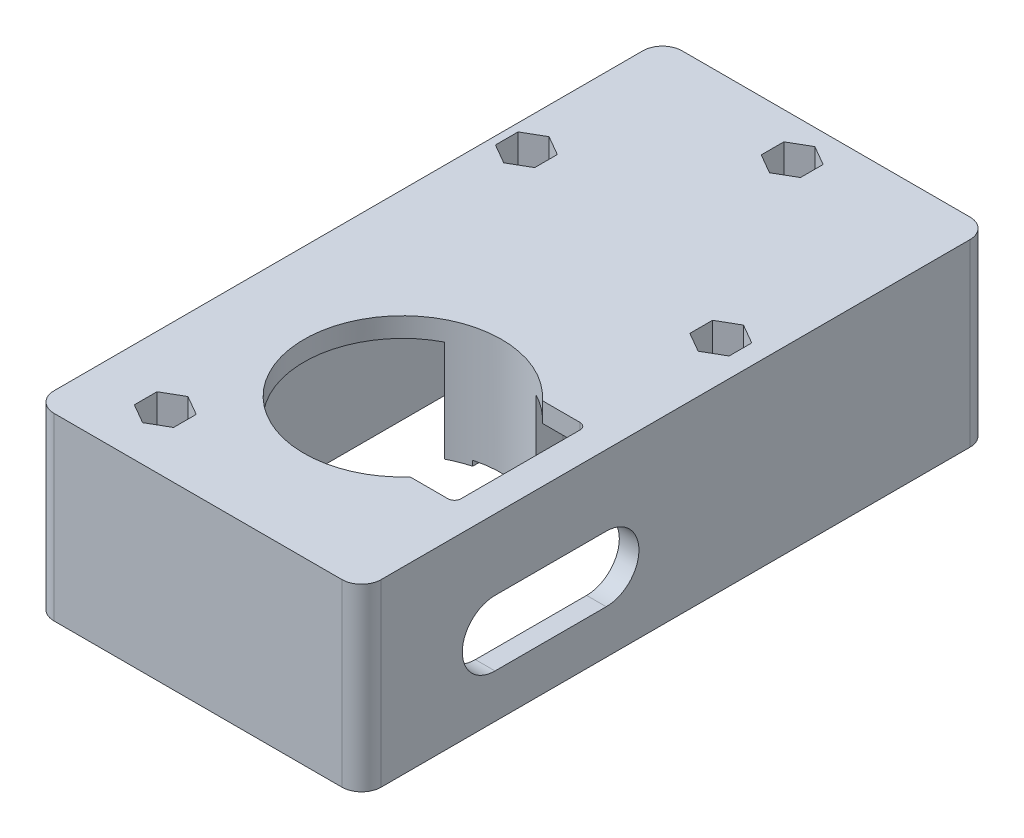
SolidWorks part; units mm, degrees
ref_plane "前视基准面" through (0, 0, 0) normal (0, 0, 1) x (1, 0, 0)
ref_plane "上视基准面" through (0, 0, 0) normal (0, 1, 0) x (1, 0, 0)
ref_plane "右视基准面" through (0, 0, 0) normal (1, 0, 0) x (0, 0, -1)
sketch "草图1" plane through (0, 0, 0) normal (0, 0, 1) x (1, 0, 0)
  line L1 (50, 38) -> (0, 38)
  line L2 (50, 38) -> (50, 0)
  line L3 (50, 0) -> (0, 0)
  line L4 (0, 38) -> (0, 0)
  dimension "D1" = 50
  dimension "D2" = 38
extrude "凸台-拉伸1" add sketch "草图1" against normal blind 3
sketch "草图2" plane through (0, 0, 0) normal (0, 0, 1) x (1, 0, 0)
  line L8 (50, 0) -> (50, 38)
  line L9 (50, 38) -> (0, 38)
  line L10 (0, 38) -> (0, 0)
  line L11 (0, 0) -> (50, 0)
  line L12 (50, 0) -> (50, 38)
  line L13 (50, 38) -> (0, 38)
  line L14 (0, 38) -> (0, 0)
  line L15 (0, 0) -> (50, 0)
  line L20 (47, 3) -> (47, 35)
  line L21 (47, 35) -> (3, 35)
  line L22 (3, 35) -> (3, 3)
  line L23 (3, 3) -> (47, 3)
  line L24 (47, 3) -> (47, 35)
  line L25 (47, 35) -> (3, 35)
  line L26 (3, 35) -> (3, 3)
  line L27 (3, 3) -> (47, 3)
  dimension "D1" = 0
  dimension "D2" = 3
extrude "凸台-拉伸2" add sketch "草图2" along normal blind 90
sketch "草图4" plane through (0, 0, -3) normal (0, 0, -1) x (-1, 0, 0)
  line L0 (-50, 38) -> (0, 38) construction
  line L1 (0, 38) -> (0, 0) construction
  circle A0 centre (-12.5, 10.5) radius 7.3
  dimension "D1" = 14.6
  dimension "D3" = 12.5
  dimension "D2" = 27.5
extrude "切除-拉伸1" cut sketch "草图4" against normal blind 45.2
sketch "草图5" plane through (0, 0, 0) normal (0, 0, 1) x (1, 0, 0)
  circle A0 centre (12.5, 10.5) radius 7.3
  circle A1 centre (12.5, 10.5) radius 7.3 construction
  circle A2 centre (12.5, 10.5) radius 10.3
  dimension "D1" = 3
extrude "凸台-拉伸3" add sketch "草图5" along normal blind 16
sketch "草图6" plane through (0, 0, -3) normal (0, 0, -1) x (-1, 0, 0)
  circle A0 centre (-12.5, 10.5) radius 5.8
  circle A3 centre (-12.5, 10.5) radius 7.3 construction
  circle A4 centre (-12.5, 10.5) radius 8.3
  circle A5 centre (-12.5, 10.5) radius 8.3
  dimension "D1" = 1
  dimension "D2" = 1.5
extrude "凸台-拉伸5" add sketch "草图6" against normal blind 1
sketch "草图7" plane through (0, 0, 16) normal (0, 0, 1) x (1, 0, 0)
  line L2 (5.4403, 3) -> (19.5597, 3)
  line L4 (5.4403, 3) -> (19.5597, 3)
  line L5 (3, 14.4799) -> (3, 6.5201)
  line L8 (3, 14.4799) -> (3, 6.5201)
  arc A1 (3, 6.5201) -> (5.4403, 3) centre (12.5, 10.5) ccw
  arc A2 (3, 6.5201) -> (5.4403, 3) centre (12.5, 10.5) ccw
  circle A3 centre (12.5, 10.5) radius 4.3
  arc A10 (19.5597, 3) -> (3, 14.4799) centre (12.5, 10.5) ccw
  arc A11 (19.5597, 3) -> (3, 14.4799) centre (12.5, 10.5) ccw
  dimension "D2" = 8.6
  dimension "D1" = 0
extrude "凸台-拉伸6" add sketch "草图7" along normal blind 2
sketch "草图8" plane through (0, 0, 18) normal (0, 0, 1) x (1, 0, 0)
  circle A1 centre (12.5, 10.5) radius 6.3
  circle A2 centre (12.5, 10.5) radius 4.3
  circle A3 centre (12.5, 10.5) radius 4.3
  dimension "D1" = 0
  dimension "D2" = 2
extrude "凸台-拉伸7" add sketch "草图8" along normal blind 10
sketch "草图9" plane through (0, 0, 28) normal (0, 0, 1) x (1, 0, 0)
  line L0 (8.2, 10.5) -> (16.8, 10.5) construction
  line L2 (16.1644, 8.25) -> (18.8, 8.25)
  line L3 (16.1644, 8.25) -> (16.1644, 12.75)
  line L4 (16.1644, 12.75) -> (18.8, 12.75)
  line L5 (18.8, 8.25) -> (18.8, 12.75)
  circle A0 centre (12.5, 10.5) radius 4.3 construction
  circle A1 centre (12.5, 10.5) radius 6.3 construction
  dimension "D1" = 4.5
extrude "切除-拉伸2" cut sketch "草图9" against normal blind 4
sketch "草图10" plane through (0, 3, 0) normal (0, 1, 0) x (1, 0, 0)
  line L0 (19.33, -36.76) -> (19.33, -34.76)
  line L1 (19.33, -34.76) -> (22.03, -34.76)
  line L2 (22.03, -34.76) -> (22.03, -36.76)
  line L3 (22.03, -36.76) -> (19.33, -36.76)
  line L8 (23.23, -37.46) -> (23.23, -28) construction
  line L9 (23.43, -37.46) -> (23.03, -37.46) construction
  line L10 (16.8, -28) -> (29.66, -28) construction
  line L11 (27.13, -34.76) -> (24.43, -34.76)
  line L12 (24.43, -34.76) -> (24.43, -36.76)
  line L13 (24.43, -36.76) -> (27.13, -36.76)
  line L14 (27.13, -36.76) -> (27.13, -34.76)
  line L15 (18.53, -37.26) -> (18.53, -34.14) construction
  line L16 (22.83, -37.26) -> (22.83, -34.14) construction
  line L17 (20.92, -34.36) -> (18.92, -34.36) construction
  circle A0 centre (19.92, -32.88) radius 0.7
  circle A1 centre (26.54, -32.88) radius 0.7
  circle A2 centre (19.92, -32.88) radius 0.98 construction
  point P14 (18.53, -35.7)
  dimension "D1" = 1.4
  dimension "D2" = 0.28
  dimension "D3" = 0.8
  dimension "D4" = 0.8
  dimension "D5" = 0.4
  dimension "D6" = 2
extrude "凸台-拉伸8" add sketch "草图10" along normal blind 32
sketch "草图11" plane through (0, 3, 0) normal (0, 1, 0) x (1, 0, 0)
  line L0 (16.8, -34.14) -> (16.8, -28) construction
  line L1 (16.2, -36.76) -> (30.26, -36.76)
  line L2 (16.2, -36.76) -> (16.2, -27.4)
  line L3 (16.2, -27.4) -> (30.26, -27.4)
  line L4 (30.26, -36.76) -> (30.26, -27.4)
  line L5 (29.66, -28) -> (29.66, -34.14) construction
  line L6 (19.33, -36.76) -> (22.03, -36.76) construction
  line L7 (16.8, -28) -> (29.66, -28) construction
  dimension "D1" = 0.6
  dimension "D2" = 0.6
  dimension "D3" = 0.6
extrude "凸台-拉伸9" add sketch "草图11" along normal blind 4.4
sketch "草图12" plane through (0, 35, 0) normal (0, -1, 0) x (1, 0, 0)
  line L1 (16.2, 27.4) -> (30.26, 27.4)
  line L2 (16.2, 27.4) -> (16.2, 36.76)
  line L3 (16.2, 36.76) -> (30.26, 36.76)
  line L4 (30.26, 27.4) -> (30.26, 36.76)
extrude "凸台-拉伸10" add sketch "草图12" along normal blind 21.2
sketch "草图13" plane through (0, 38, 0) normal (0, 1, 0) x (1, 0, 0)
  line L0 (12.3, -64.096) -> (42.5, -64.096) construction
  line L1 (40.04, -72.896) -> (39.0237, -72.896) construction
  line L2 (38.625, -74.196) -> (44.4, -74.196)
  line L3 (45.4, -73.196) -> (45.4, -54.996)
  line L4 (44.4, -57.796) -> (44.4, -70.396) construction
  line L5 (38.625, -53.996) -> (44.4, -53.996)
  circle A0 centre (27.4, -64.096) radius 15.1 construction
  circle A1 centre (27.4, -64.096) radius 14.1 construction
  arc A2 (38.625, -74.196) -> (38.625, -53.996) centre (27.4, -64.096) cw
  arc A3 (44.4, -53.996) -> (45.4, -54.996) centre (44.4, -54.996) cw
  arc A4 (44.4, -74.196) -> (45.4, -73.196) centre (44.4, -73.196) ccw
  point P16 (45.4, -64.096)
  point P18 (45.4, -53.996)
  point P21 (45.4, -74.196)
  dimension "D1" = 1
  dimension "D2" = 1.3
  dimension "D4" = 1
  dimension "D3" = 1
extrude "切除-拉伸3" cut sketch "草图13" against normal blind 3
sketch "草图14" plane through (0, 35, 0) normal (0, -1, 0) x (1, 0, 0)
  line L0 (14.3, 64.096) -> (40.5, 64.096) construction
  line L1 (23.9, 46.596) -> (23.9, 50.4373) construction
  line L2 (30.9, 46.596) -> (30.9, 50.4373) construction
  line L3 (23.9, 46.596) -> (23.9, 49.4072)
  line L4 (30.9, 46.596) -> (30.9, 49.4072)
  line L5 (30.9, 81.596) -> (30.9, 78.7847)
  line L6 (23.9, 81.596) -> (23.9, 78.7847)
  circle A0 centre (27.4, 46.596) radius 1.65
  circle A1 centre (27.4, 64.096) radius 13.1 construction
  arc A2 (23.9, 49.4072) -> (30.9, 49.4072) centre (27.4, 64.096) ccw
  arc A3 (38.625, 74.196) -> (38.625, 53.996) centre (27.4, 64.096) ccw construction
  arc A4 (23.9, 46.596) -> (30.9, 46.596) centre (27.4, 46.596) ccw
  arc A5 (23.9, 46.596) -> (30.9, 46.596) centre (27.4, 46.596) ccw construction
  arc A6 (23.9, 81.596) -> (30.9, 81.596) centre (27.4, 81.596) cw
  arc A7 (23.9, 78.7847) -> (30.9, 78.7847) centre (27.4, 64.096) cw
  circle A8 centre (27.4, 81.596) radius 1.65
  dimension "D1" = 3.3
extrude "凸台-拉伸11" add sketch "草图14" along normal blind 15.5
sketch "草图15" plane through (0, 35, 0) normal (0, -1, 0) x (1, 0, 0)
  line L0 (23.9, 46.596) -> (23.9, 50.4373) construction
  line L1 (20.4, 50.7165) -> (20.4, 46.596)
  line L2 (27.4, 48.696) -> (27.4, 44.496) construction
  line L4 (34.4, 50.7165) -> (34.4, 46.596)
  line L5 (45.4, 64.096) -> (12.3, 64.096) construction
  line L6 (45.4, 73.196) -> (45.4, 54.996) construction
  line L7 (20.4, 77.4754) -> (20.4, 81.596)
  line L8 (34.4, 77.4754) -> (34.4, 81.596)
  circle A0 centre (27.4, 46.596) radius 1.65
  circle A1 centre (27.4, 46.596) radius 2.1 construction
  arc A2 (20.4, 46.596) -> (34.4, 46.596) centre (27.4, 46.596) ccw
  arc A3 (20.4, 50.7165) -> (34.4, 50.7165) centre (27.4, 64.096) ccw
  arc A4 (23.9, 78.7847) -> (23.9, 49.4072) centre (27.4, 64.096) ccw construction
  arc A5 (20.4, 77.4754) -> (34.4, 77.4754) centre (27.4, 64.096) cw
  circle A6 centre (27.4, 81.596) radius 1.65
  arc A7 (20.4, 81.596) -> (34.4, 81.596) centre (27.4, 81.596) cw
  arc A9 (30.9, 49.4072) -> (38.625, 53.996) centre (27.4, 64.096) ccw construction
  line M14 (23.9, 78.7847) -> (23.9, 81.596)
  arc M15 (23.9, 81.596) -> (30.9, 81.596) centre (27.4, 81.596) cw
  line M16 (30.9, 81.596) -> (30.9, 78.7847)
  line M24 (30.9, 49.4072) -> (30.9, 46.596)
  arc M25 (30.9, 46.596) -> (23.9, 46.596) centre (27.4, 46.596) cw
  line M26 (23.9, 46.596) -> (23.9, 49.4072)
  dimension "D1" = 3.3
  dimension "D2" = 7
extrude "凸台-拉伸12" add sketch "草图15" along normal blind 15.5 contours L1 A2 L4 M24 M25 M26 | A7 L7 L8 M14 M15 M16 region at (22.0467, 35, 49.7857) region at (20.5788, 35, 79.5357)
sketch "草图16" plane through (0, 19.5, 0) normal (0, -1, 0) x (1, 0, 0)
  line L0 (45.4, 64.096) -> (12.3, 64.096) construction
  line L1 (45.4, 73.196) -> (45.4, 54.996) construction
  line L24 (31.3, 81.596) -> (31.3, 77.2291)
  line L25 (23.5, 77.2291) -> (23.5, 81.596)
  line L26 (31.3, 46.596) -> (31.3, 50.9628)
  line L27 (23.5, 50.9628) -> (23.5, 46.596)
  line L28 (31.3, 46.596) -> (31.3, 50.9628)
  line L29 (23.5, 50.9628) -> (23.5, 46.596)
  arc A0 (20.4, 77.4754) -> (20.4, 50.7165) centre (27.4, 64.096) ccw construction
  arc A25 (23.5, 81.596) -> (31.3, 81.596) centre (27.4, 81.596) cw
  arc A26 (23.5, 77.2291) -> (31.3, 77.2291) centre (27.4, 64.096) cw
  arc A27 (23.5, 50.9628) -> (31.3, 50.9628) centre (27.4, 64.096) ccw
  arc A28 (23.5, 46.596) -> (31.3, 46.596) centre (27.4, 46.596) ccw
  arc A29 (23.5, 50.9628) -> (31.3, 50.9628) centre (27.4, 64.096) ccw
  arc A30 (23.5, 46.596) -> (31.3, 46.596) centre (27.4, 46.596) ccw
  dimension "D1" = 0.4
extrude "切除-拉伸4" cut sketch "草图16" against normal blind 0.8
sketch "草图17" plane through (0, 0, 0) normal (0, 0, 1) x (1, 0, 0)
  line L1 (3, 3) -> (47, 3) construction
  line L2 (22.83, 10.5392) -> (22.83, 3)
  line L3 (22.83, 10.2892) -> (22.83, 10.7892) construction
  line L4 (22.83, 3) -> (19.5597, 3)
  line L5 (5.4403, 3) -> (3, 3)
  line L6 (3, 3) -> (3, 6.5201)
  line L7 (3, 14.4799) -> (3, 35)
  line L8 (3, 35) -> (22.83, 35)
  line L9 (47, 35) -> (3, 35) construction
  line L10 (22.83, 10.5392) -> (22.83, 35)
  arc A1 (5.4403, 3) -> (3, 6.5201) centre (12.5, 10.5) cw
  arc A2 (3, 6.5201) -> (5.4403, 3) centre (12.5, 10.5) ccw construction
  arc A3 (3, 14.4799) -> (19.5597, 3) centre (12.5, 10.5) cw
  arc M1 (3, 14.4799) -> (19.5597, 3) centre (12.5, 10.5) cw
  line M2 (19.5597, 3) -> (47, 3)
  line M4 (47, 35) -> (3, 35)
  line M5 (3, 35) -> (3, 14.4799)
extrude "凸台-拉伸13" add sketch "草图17" along normal blind 18 contours L2 L10 M4 M5 M1 M2 | L5 A1 L6 region at (13.2696, 26.2496, 0) region at (3.7547, 4.0789, 0)
sketch "草图18" plane through (0, 0, 18) normal (0, 0, 1) x (1, 0, 0)
  line L8 (3, 35) -> (3, 3)
  line L9 (3, 3) -> (22.83, 3)
  line L10 (22.83, 3) -> (22.83, 35)
  line L11 (22.83, 35) -> (3, 35)
  line L12 (3, 35) -> (3, 3)
  line L13 (3, 3) -> (22.83, 3)
  line L14 (22.83, 3) -> (22.83, 35)
  line L15 (22.83, 35) -> (3, 35)
  circle A0 centre (12.5, 10.5) radius 6.3
  circle A1 centre (12.5, 10.5) radius 6.3 construction
  dimension "D1" = 0
extrude "凸台-拉伸14" add sketch "草图18" along normal blind 10
sketch "草图19" plane through (0, 0, 28) normal (0, 0, 1) x (1, 0, 0)
  line L0 (18.3845, 8.25) -> (22.83, 8.25)
  line L1 (22.83, 7.4) -> (22.83, 13.8) construction
  line L2 (22.83, 8.25) -> (22.83, 12.75)
  line L3 (22.83, 12.75) -> (18.3845, 12.75)
  line L4 (18.3845, 12.75) -> (16.1644, 12.75) construction
  line L5 (18.3845, 8.25) -> (18.3845, 12.75)
extrude "切除-拉伸5" cut sketch "草图19" against normal blind 4
sketch "草图23" plane through (0, 35, 0) normal (0, -1, 0) x (1, 0, 0)
  line L0 (22.83, 27.4) -> (22.83, 0) construction
  line L1 (22.83, 0) -> (47, 0) construction
  line L2 (22.83, 0) -> (22.83, 9)
  line L3 (22.83, 0) -> (31.83, 0)
  line L4 (47, 90) -> (47, 0) construction
  line L5 (44, 26.08) -> (47, 26.08)
  line L6 (47, 26.08) -> (47, 38.08)
  line L7 (45.65, 32.08) -> (42.35, 32.08) construction
  line L8 (44, 38.08) -> (47, 38.08)
  line L9 (30.26, 32.08) -> (42.35, 32.08) construction
  line L10 (30.26, 36.76) -> (30.26, 27.4) construction
  line L11 (3, 90) -> (3, 28) construction
  line L12 (0, 90) -> (50, 90) construction
  line L13 (11, 82.35) -> (11, 85.65) construction
  line L14 (5, 90) -> (5, 84)
  line L15 (17, 90) -> (17, 84)
  line L16 (5, 90) -> (17, 90)
  circle A0 centre (25.83, 3) radius 1.65
  arc A1 (31.83, 0) -> (22.83, 9) centre (22.83, 0) ccw
  circle A2 centre (44, 32.08) radius 1.65
  arc A3 (44, 26.08) -> (44, 38.08) centre (44, 32.08) cw
  circle A4 centre (11, 84) radius 1.65
  arc A5 (5, 84) -> (17, 84) centre (11, 84) ccw
  point P22 (47, 32.08)
  dimension "D1" = 3
  dimension "D4" = 3.3
  dimension "D5" = 3
  dimension "D6" = 3.3
  dimension "D7" = 6
  dimension "D8" = 3.3
  dimension "D9" = 8
  dimension "D10" = 6
  dimension "D11" = 6
  dimension "D2" = 3
  dimension "D3" = 9
extrude "凸台-拉伸16" add sketch "草图23" along normal through all
sketch "草图25" plane through (0, 35, 0) normal (0, -1, 0) x (1, 0, 0)
  line L0 (0, -3) -> (0, 90) construction
  line L1 (16.2, 28) -> (3, 28) construction
  circle A0 centre (4.2, 22) radius 1.65
  circle A1 centre (4.2, 22) radius 3 construction
  circle A2 centre (25.83, 3) radius 1.65
  circle A7 centre (44, 32.08) radius 1.65
  circle A8 centre (44, 32.08) radius 1.65
  circle A10 centre (11, 84) radius 1.65
  circle A11 centre (11, 84) radius 1.65
  dimension "D1" = 3.3
  dimension "D2" = 6
  dimension "D3" = 4.2
  dimension "D4" = 6
  dimension "D5" = 0
  dimension "D6" = 0
extrude "切除-拉伸7" cut sketch "草图25" against normal through all and the other way through all
sketch "草图26" plane through (0, 38, 0) normal (0, 1, 0) x (1, 0, 0)
  line L0 (0, 3) -> (0, -90) construction
  line L1 (4.2, -18.5371) -> (1.201, -20.2685)
  line L2 (1.201, -20.2685) -> (1.201, -23.7315)
  line L3 (1.201, -23.7315) -> (4.2, -25.4629)
  line L4 (4.2, -25.4629) -> (7.199, -23.7315)
  line L5 (7.199, -23.7315) -> (7.199, -20.2685)
  line L6 (7.199, -20.2685) -> (4.2, -18.5371)
  line L7 (25.83, -6.4629) -> (28.829, -4.7315)
  line L8 (28.829, -4.7315) -> (28.829, -1.2685)
  line L9 (28.829, -1.2685) -> (25.83, 0.4629)
  line L10 (25.83, 0.4629) -> (22.831, -1.2685)
  line L11 (22.831, -1.2685) -> (22.831, -4.7315)
  line L12 (22.831, -4.7315) -> (25.83, -6.4629)
  line L14 (11, -80.5371) -> (8.001, -82.2685)
  line L15 (8.001, -82.2685) -> (8.001, -85.7315)
  line L16 (8.001, -85.7315) -> (11, -87.4629)
  line L17 (11, -87.4629) -> (13.999, -85.7315)
  line L18 (13.999, -85.7315) -> (13.999, -82.2685)
  line L19 (13.999, -82.2685) -> (11, -80.5371)
  line L20 (44, -28.6171) -> (41.001, -30.3485)
  line L21 (41.001, -30.3485) -> (41.001, -33.8115)
  line L22 (41.001, -33.8115) -> (44, -35.5429)
  line L23 (44, -35.5429) -> (46.999, -33.8115)
  line L24 (46.999, -33.8115) -> (46.999, -30.3485)
  line L25 (46.999, -30.3485) -> (44, -28.6171)
  circle A0 centre (4.2, -22) radius 2.999 construction
  circle A1 centre (25.83, -3) radius 2.999 construction
  circle A2 centre (11, -84) radius 2.999 construction
  circle A3 centre (44, -32.08) radius 2.999 construction
  dimension "D1" = 5.998
extrude "切除-拉伸8" cut sketch "草图26" against normal blind 24.5
sketch "草图29" plane through (0, 0, 90) normal (0, 0, 1) x (1, 0, 0)
  line L8 (0, 0) -> (50, 0)
  line L9 (50, 0) -> (50, 38)
  line L10 (50, 38) -> (0, 38)
  line L11 (0, 38) -> (0, 0)
  line L12 (0, 0) -> (50, 0)
  line L13 (50, 0) -> (50, 38)
  line L14 (50, 38) -> (0, 38)
  line L15 (0, 38) -> (0, 0)
  dimension "D1" = 0
extrude "凸台-拉伸17" add sketch "草图29" along normal blind 3
ref_plane "基准面3" through (0, 10.5, 0) normal (0, 1, 0) x (1, 0, 0)
sketch "草图30" plane through (50, 0, 0) normal (1, 0, 0) x (0, 0, -1)
  line L1 (-93, 10.51) -> (3, 10.51)
  line L2 (-93, 10.51) -> (-93, 10.49)
  line L3 (-93, 10.49) -> (3, 10.49)
  line L4 (3, 10.51) -> (3, 10.49)
  line L6 (27.5, 10.5) -> (-27.5, 10.5) construction
  line L7 (3, 0) -> (3, 38) construction
  line L8 (-93, 0) -> (-93, 38) construction
  point P6 (0, 0)
  point P10 (0, 0)
  point P12 (0, 0)
  dimension "D1" = 0.01
  dimension "D2" = 0.01
  dimension "D3" = 0.02
extrude "切除-拉伸9" cut sketch "草图30" against normal through all
delete or keep bodies "实体-删除/保留 1" type delete bodies bodies 132
fillet "圆角1" radius 3 4 edges at (0, 24.255, -3) (0, 24.255, 93) (50, 24.255, 93) (50, 24.255, -3)
sketch "草图32" plane through (50, 0, 0) normal (1, 0, 0) x (0, 0, -1)
  circle A0 centre (-63.8247, 19.6279) radius 6.0017
sketch "草图33" plane through (50, 0, 0) normal (1, 0, 0) x (0, 0, -1)
  line L0 (-55.596, 22.2) -> (-72.596, 22.2) construction
  line L1 (-55.596, 17.2) -> (-72.596, 17.2)
  line L2 (-55.596, 27.2) -> (-72.596, 27.2)
  line L3 (-64.096, 19.2) -> (-64.096, 34.9) construction
  line L4 (-57.796, 19.2) -> (-70.396, 19.2) construction
  line L5 (-57.796, 34.9) -> (-70.396, 34.9) construction
  arc A0 (-55.596, 17.2) -> (-55.596, 27.2) centre (-55.596, 22.2) ccw
  arc A1 (-72.596, 27.2) -> (-72.596, 17.2) centre (-72.596, 22.2) ccw
  point P2 (-64.096, 22.2)
  dimension "D2" = 5
  dimension "D1" = 17
  dimension "D3" = 3
extrude "切除-拉伸10" cut sketch "草图33" against normal blind 3
